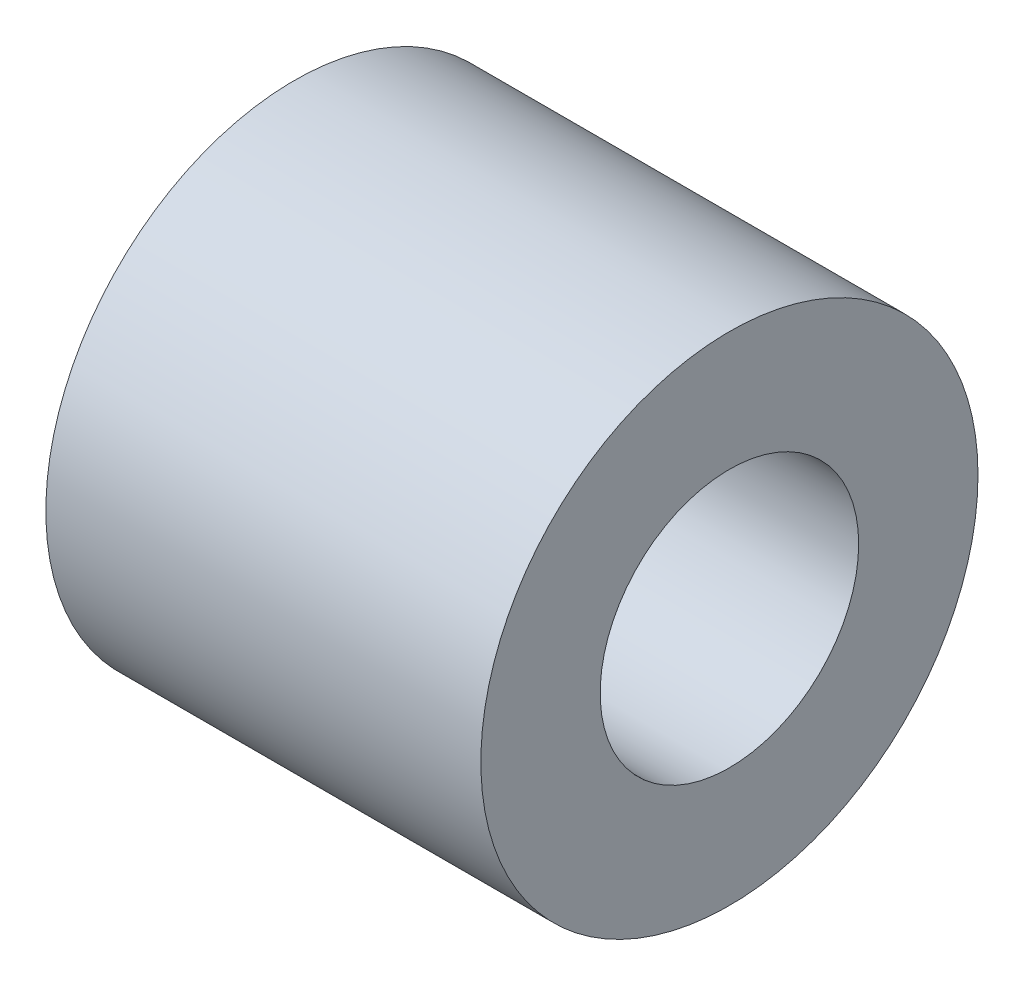
SolidWorks part; units mm, degrees
ref_plane "Front Plane" through (0, 0, 0) normal (0, 0, 1) x (1, 0, 0)
ref_plane "Top Plane" through (0, 0, 0) normal (0, 1, 0) x (1, 0, 0)
ref_plane "Right Plane" through (0, 0, 0) normal (1, 0, 0) x (0, 0, -1)
sketch "Sketch1" plane through (0, 0, 0) normal (1, 0, 0) x (0, 0, -1)
  circle A0 centre (0, 0) radius 6.35
  circle A1 centre (0, 0) radius 3.302
  dimension "D1" = 6.604
  dimension "D2" = 12.7
extrude "Boss-Extrude1" add sketch "Sketch1" along normal blind 11.1125
